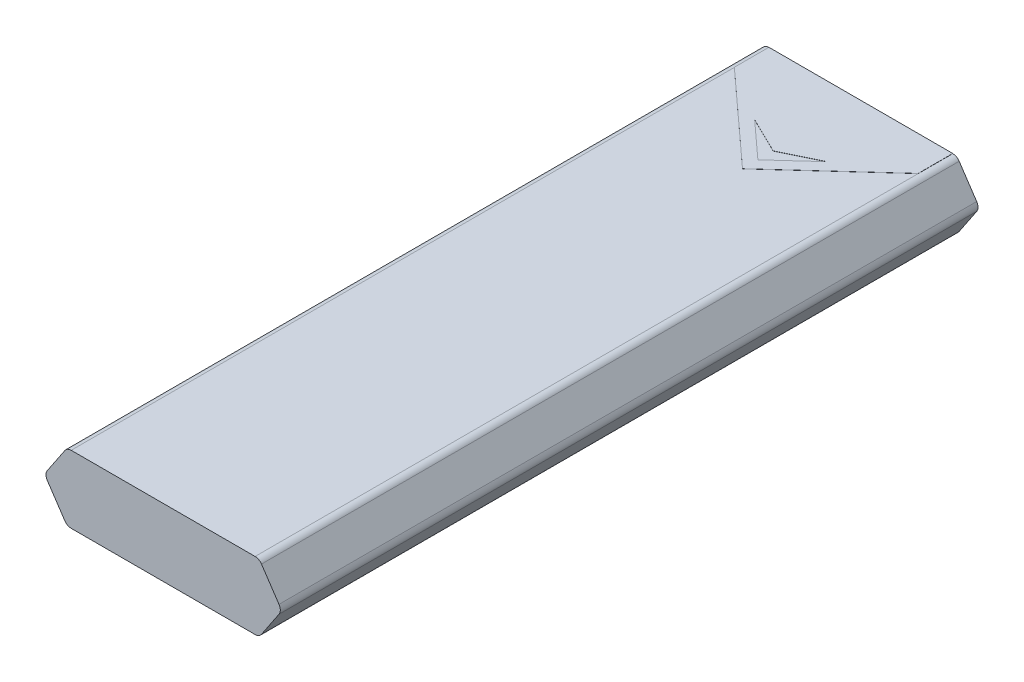
SolidWorks part; units mm, degrees
ref_plane "Front Plane" through (0, 0, 0) normal (0, 0, 1) x (1, 0, 0)
ref_plane "Top Plane" through (0, 0, 0) normal (0, 1, 0) x (1, 0, 0)
ref_plane "Right Plane" through (0, 0, 0) normal (1, 0, 0) x (0, 0, -1)
sketch "Sketch1" plane through (0, 0, 0) normal (0, 0, 1) x (1, 0, 0)
  line L0 (0, 0) -> (19.6215, 0) construction
  line L1 (0, 0) -> (-19.6215, 0) construction
  line L2 (0, 0) -> (0, 5.588) construction
  line L3 (0, 0) -> (0, -5.588) construction
  line L4 (-15.875, -5.588) -> (-15.875, 5.588) construction
  line L5 (-15.875, -5.588) -> (15.875, -5.588)
  line L6 (-15.875, 5.588) -> (15.875, 5.588)
  line L7 (15.875, -5.588) -> (15.875, 5.588) construction
  line L8 (-15.875, -5.588) -> (15.875, 5.588) construction
  line L9 (-15.875, 5.588) -> (15.875, -5.588) construction
  line L10 (-15.875, 5.588) -> (-19.6215, 0)
  line L11 (-19.6215, 0) -> (-15.875, -5.588)
  line L12 (15.875, -5.588) -> (19.6215, 0)
  line L13 (19.6215, 0) -> (15.875, 5.588)
  point P6 (10.7546, 3.2031)
  point P7 (10.1554, 5.588)
  dimension "D1" = 39.243
  dimension "D2" = 11.176
  dimension "D3" = 31.75
extrude "Boss-Extrude1" add sketch "Sketch1" along normal blind 115.316 contours L6 L13 L12 L5 L11 L10
sketch "Sketch2" plane through (0, 0, 0) normal (0, 0, -1) x (-1, 0, 0)
  line L0 (0, 0) -> (0, 1.1938) construction
  line L1 (-4.1275, 1.1938) -> (4.1275, 1.1938) construction
  line L2 (-4.1275, 1.1938) -> (-4.1275, -1.1938) construction
  line L3 (-4.1275, -1.1938) -> (4.1275, -1.1938) construction
  line L4 (4.1275, 1.1938) -> (4.1275, -1.1938) construction
  line L5 (-4.1275, 1.1938) -> (4.1275, -1.1938) construction
  line L6 (-4.1275, -1.1938) -> (4.1275, 1.1938) construction
  line L8 (-2.9337, 1.1938) -> (2.9337, 1.1938)
  line L9 (-2.9337, 1.1938) -> (-2.9337, -1.1938)
  line L10 (-2.9337, -1.1938) -> (2.9337, -1.1938)
  line L11 (2.9337, 1.1938) -> (2.9337, -1.1938)
  circle A0 centre (-2.9337, 0) radius 1.1938
  circle A1 centre (2.9337, 0) radius 1.1938
  point P0 (0, 0)
  dimension "D1" = 2.3876
  dimension "D2" = 8.255
extrude "Cut-Extrude1" cut sketch "Sketch2" against normal blind 6.985 contours A0
extrude "Cut-Extrude2" cut sketch "Sketch2<4>" against normal blind 6.985 contours A1
sketch "Sketch2<4>" plane through (0, 0, 0) normal (0, 0, -1) x (-1, 0, 0) same geometry as "Sketch2"
extrude "Cut-Extrude3" cut sketch "Sketch2<5>" against normal blind 6.985 contours L8 L11 L10 L9
sketch "Sketch2<5>" plane through (0, 0, 0) normal (0, 0, -1) x (-1, 0, 0) same geometry as "Sketch2"
fillet "Fillet1" radius 1.27 6 edges at (15.875, 5.588, 57.658) (19.6215, 0, 57.658) (15.875, -5.588, 57.658) (-15.875, -5.588, 57.658) (-19.6215, 0, 57.658) (-15.875, 5.588, 57.658)
sketch "Sketch4" plane through (0, 5.588, 0) normal (0, 1, 0) x (1, 0, 0)
  line L0 (-15.1975, 0) -> (-15.1975, -115.316) construction
  line L1 (15.1975, 0) -> (-15.1975, 0)
  line L2 (15.1975, 0) -> (15.1975, -5.715)
  line L3 (15.1975, -5.715) -> (-15.1975, -5.715) construction
  line L4 (-15.1975, 0) -> (-15.1975, -5.715)
  line L5 (0, 0) -> (0, -19.558) construction
  line L6 (15.1975, -5.715) -> (0, -19.558)
  line L7 (0, -19.558) -> (-15.1975, -5.715)
  dimension "D1" = 5.715
  dimension "D2" = 19.558
extrude "Boss-Extrude2" add sketch "Sketch4" along normal blind 0.0254 contours L7 L4 L1 L2 L6
mirror "Mirror1" about plane through (0, 0, 0) normal (0, 1, 0) of "Boss-Extrude2"
sketch "Sketch6" plane through (0, 5.6134, 0) normal (0, 1, 0) x (1, 0, 0)
  line L0 (0, 0) -> (0, -19.558) construction
  line L1 (15.1975, 0) -> (-15.1975, 0) construction
  line L2 (0, -19.558) -> (-15.1975, -5.715) construction
  line L3 (15.1975, -5.715) -> (0, -19.558) construction
  line L4 (0, -17.018) -> (-6.0095, -11.5441)
  line L5 (-6.0095, -11.5441) -> (0, -14.478)
  line L6 (0, -14.478) -> (6.0095, -11.5441)
  line L7 (6.0095, -11.5441) -> (0, -17.018)
  line L8 (0, -19.558) -> (-15.1975, -5.715) construction
  point P14 (5.8083, -12.2965)
  dimension "D1" = 2.54
  dimension "D2" = 2.54
extrude "Cut-Extrude5" cut sketch "Sketch6" against normal blind 0.0254 contours L4 L5 L6 L7
